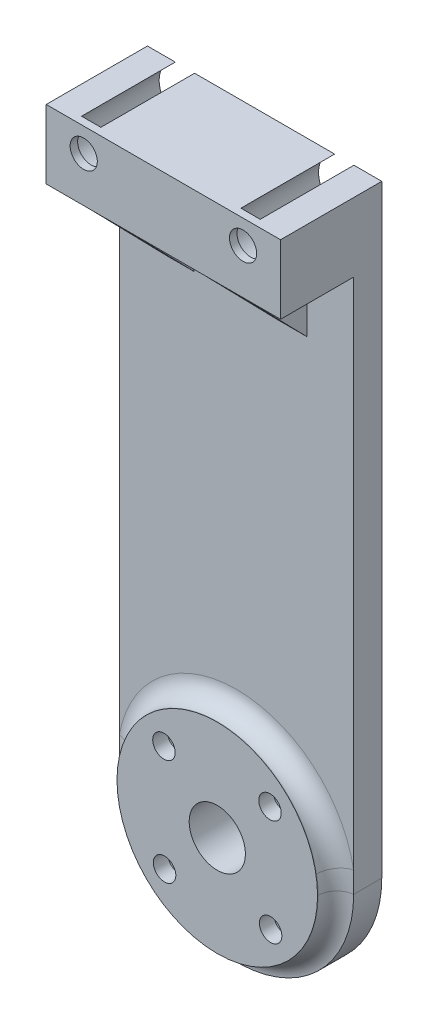
SolidWorks part; units mm, degrees
ref_plane "Plano frontal" through (0, 0, 0) normal (0, 0, 1) x (1, 0, 0)
ref_plane "Plano superior" through (0, 0, 0) normal (0, 1, 0) x (1, 0, 0)
ref_plane "Plano direito" through (0, 0, 0) normal (1, 0, 0) x (0, 0, -1)
sketch "Esboço1" plane through (0, 0, 0) normal (0, 0, -1) x (-1, 0, 0)
  circle A5 centre (0, 0) radius 10.7 construction
  circle A7 centre (0, 0) radius 10.7
extrude "Ressalto-extrusão1" add sketch "Esboço1" along normal offset from surface (2.05 mm away) 2 offset beyond the face yes
sketch "Esboço2" plane through (0, 0, -2.05) normal (0, 0, -1) x (-1, 0, 0)
  line L1 (-12.5, 64.3883) -> (12.5, 64.3883)
  line L3 (9.2, 64.6383) -> (-9.2, 64.6383) construction
  line L6 (-12.5, 64.3883) -> (-12.5, 0)
  line L9 (12.5, 64.3883) -> (12.5, 0)
  circle A10 centre (8.5, 61.8383) radius 2 construction
  circle A17 centre (-8.5, 61.8383) radius 2.25 construction
  arc A19 (12.5, 0) -> (-12.5, 0) centre (0, 0) cw
  dimension "D1" = 4
  dimension "D2" = 4
  dimension "D3" = 0.25
extrude "Ressalto-extrusão2" add sketch "Esboço2" along normal blind 3
sketch "Esboço4" plane through (0, 0, -5.05) normal (0, 0, -1) x (-1, 0, 0)
  line L1 (-12.5, 64.3883) -> (12.5, 64.3883)
  line L2 (-12.5, 64.3883) -> (-12.5, 57.0383)
  line L3 (-12.5, 57.0383) -> (12.5, 57.0383)
  line L4 (12.5, 64.3883) -> (12.5, 57.0383)
  line L5 (12.5, 0) -> (12.5, 64.3883) construction
  line L6 (-12.7, 59.0383) -> (12.7, 59.0383) construction
  dimension "D1" = 2
extrude "Ressalto-extrusão3" add sketch "Esboço4" against normal up to surface (10.8 mm away)
hole_wizard "Rebaixo para SHCS M2.51" positions "Sketch1" profile "Sketch2" counterbore size "M2.5" standard "Ansi Metric" end condition up to next
sketch "Sketch1" plane through (0, 0, -5.05) normal (0, 0, -1) x (-1, 0, 0)
  circle A0 centre (-8.5, 61.8383) radius 1.35 construction
  circle A1 centre (8.5, 61.8383) radius 1.35 construction
  point P0 (-8.5, 61.8383)
  point P3 (8.5, 61.8383)
sketch "Sketch2" plane through (8.5, 61.8383, -5.05) normal (1, 0, 0) x (0, 1, 0)
  line L0 (0, 0) -> (0, 10.8)
  line L1 (0, 10.8) -> (1.45, 10.8)
  line L3 (1.45, 10.8) -> (1.45, 10)
  line L4 (1.45, 10) -> (2.75, 10)
  line L5 (2.75, 10) -> (2.75, 0)
  line L7 (2.75, 0) -> (0, 0)
  line L11 (0, -6.35) -> (0, 107.95) construction
  dimension "Thru Hole Dia." = 2.9
  dimension "Thru Hole Depth" = 10.8
  dimension "C'Bore Dia." = 5.5
  dimension "C'Bore Depth" = 10
hole_wizard "Rebaixo para parafuso com cabeça redonda de M21" positions "Sketch3" profile "Sketch4" counterbore size "M2" standard "DIN" end condition up to next
sketch "Sketch3" plane through (0, 0, -5.05) normal (0, 0, -1) x (-1, 0, 0)
  circle A1 centre (-5.6247, 5.6888) radius 0.8 construction
  point P26 (-5.6247, 5.6888)
sketch "Sketch4" plane through (5.6247, 5.6888, -5.05) normal (1, 0, 0) x (0, 1, 0)
  line L0 (0, 0) -> (0, 5.05)
  line L1 (0, 5.05) -> (1.2, 5.05)
  line L3 (1.2, 5.05) -> (1.2, 3.5)
  line L4 (1.2, 3.5) -> (2.2, 3.5)
  line L5 (2.2, 3.5) -> (2.2, 0)
  line L7 (2.2, 0) -> (0, 0)
  line L11 (0, -6.35) -> (0, 107.95) construction
  dimension "Thru Hole Dia." = 2.4
  dimension "Thru Hole Depth" = 5.05
  dimension "C'Bore Dia." = 4.4
  dimension "C'Bore Depth" = 3.5
pattern_circular "PadrãoCircular1" count 4 over 360 about axis through (0, 0, -5.05) along (0, 0, -1) of "Rebaixo para parafuso com cabeça redonda de M21"
sketch "Esboço5" plane through (0, 0, 0) normal (1, 0, 0) x (0, 0, -1)
  line L0 (-5.75, 57.0383) -> (2.05, 49.0383)
  line L1 (2.05, 57.0383) -> (2.05, 0) construction
  line L2 (-5.75, 57.0383) -> (2.05, 57.0383) construction
  dimension "D1" = 8
rib "Nervura1" sketch "Esboço5" sketch "Esboço5" thickness 15 extrusion direction parallel to sketch draft on no parameters "D1"=15
sketch "Esboço6" plane through (0, 0, -2.05) normal (0, 0, 1) x (1, 0, 0)
  line L0 (7.5, 49.0383) -> (-7.5, 49.0383) construction
  line L1 (4.4016, 49.0383) -> (-4.5372, 49.0383)
  line L2 (4.4016, 49.0383) -> (4.4016, 57.0383)
  line L3 (4.4016, 57.0383) -> (-4.5372, 57.0383)
  line L4 (-4.5372, 49.0383) -> (-4.5372, 57.0383)
  line L5 (4.4635, 57.1) -> (4.4021, 49.1002) construction
  line L6 (-7.5, 57.0383) -> (7.5, 57.0383) construction
  line L7 (-4.5976, 49.1693) -> (-4.5362, 57.1691) construction
extrude "Corte-extrusão1" cut sketch "Esboço6" along normal up to next
sketch "Esboço7" plane through (0, 0, -5.05) normal (0, 0, -1) x (-1, 0, 0)
  circle A0 centre (0, 0) radius 3
  dimension "D1" = 6
extrude "Corte-extrusão2" cut sketch "Esboço7" against normal up to next
fillet "Filete1" radius 2 1 edges at (-10.7, 0, -2.05)
